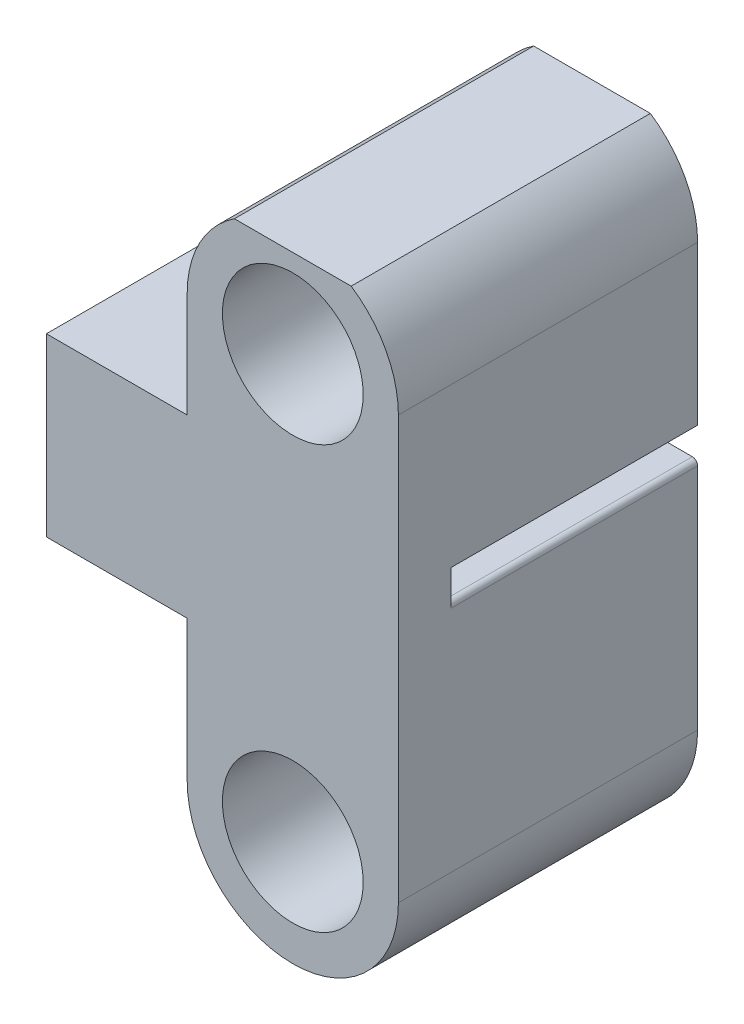
SolidWorks part; units mm, degrees
ref_plane "Front Plane" through (0, 0, 0) normal (0, 0, 1) x (1, 0, 0)
ref_plane "Top Plane" through (0, 0, 0) normal (0, 1, 0) x (1, 0, 0)
ref_plane "Right Plane" through (0, 0, 0) normal (1, 0, 0) x (0, 0, -1)
sketch "Sketch1" plane through (0, 0, 0) normal (0, 0, 1) x (1, 0, 0)
  line L0 (0, 0) -> (0, -12) construction
  line L1 (-3, 0) -> (-3, -12)
  line L2 (3, 0) -> (3, -12)
  arc A0 (3, 0) -> (-3, 0) centre (0, 0) ccw
  arc A1 (-3, -12) -> (3, -12) centre (0, -12) ccw
  circle A2 centre (0, 0) radius 2
  circle A3 centre (0, -12) radius 2
  dimension "D2" = 6
  dimension "D6" = 4
  dimension "D7" = 4
  dimension "D1" = 12
extrude "Boss-Extrude1" add sketch "Sketch1" along normal blind 8.5
sketch "Sketch2" plane through (3, 0, 0) normal (1, 0, 0) x (0, 0, -1)
  line L0 (-8.5, -6) -> (0, -6) construction
  line L1 (-8.5, -12) -> (-8.5, 0) construction
  line L2 (0, -12) -> (0, 0) construction
  line L3 (-4.25, 0) -> (-4.25, -12) construction
  line L4 (-8.5, 0) -> (0, 0) construction
  line L5 (-8.5, -12) -> (0, -12) construction
  circle A0 centre (-4.25, -8.5) radius 2
  dimension "D1" = 4
  dimension "D2" = 2.5
extrude "Cut-Extrude1" [suppressed] cut sketch "Sketch2" against normal through all
sketch "Sketch3" [suppressed] plane through (3, 0, 0) normal (1, 0, 0) x (0, 0, -1)
  line L1 (-0.6416, -8.5) -> (-2.4458, -5.375)
  line L2 (-2.4458, -5.375) -> (-6.0542, -5.375)
  line L3 (-6.0542, -5.375) -> (-7.8584, -8.5)
  line L4 (-7.8584, -8.5) -> (-6.0542, -11.625)
  line L5 (-6.0542, -11.625) -> (-2.4458, -11.625)
  line L6 (-2.4458, -11.625) -> (-0.6416, -8.5)
  line L7 (-1.8684, -4.375) -> (-6.6316, -4.375)
  line L8 (-6.6316, -4.375) -> (-9.0131, -8.5)
  line L9 (-9.0131, -8.5) -> (-6.6316, -12.625)
  line L10 (-6.6316, -12.625) -> (-1.8684, -12.625)
  line L11 (-1.8684, -12.625) -> (0.5131, -8.5)
  line L12 (0.5131, -8.5) -> (-1.8684, -4.375)
  circle A0 centre (-4.25, -8.5) radius 3.125 construction
  circle A1 centre (-4.25, -8.5) radius 4.125 construction
  dimension "D1" = 6.25
  dimension "D2" = 1
extrude "Boss-Extrude2" [suppressed] add sketch "Sketch3" along normal blind 2 and the other way blind 0.5
sketch "Sketch4" [suppressed] plane through (-3, 0, 0) normal (-1, 0, 0) x (0, 0, 1)
  line L0 (4.25, 0) -> (4.25, -6.5) construction
  line L1 (8.5, 0) -> (0, 0) construction
  line L3 (0.75, -2.75) -> (7.75, -2.75)
  line L4 (0.75, -2.75) -> (0.75, -5.75)
  line L5 (0.75, -5.75) -> (7.75, -5.75)
  line L6 (7.75, -2.75) -> (7.75, -5.75)
  line L7 (0.75, -2.75) -> (7.75, -5.75) construction
  line L8 (0.75, -5.75) -> (7.75, -2.75) construction
  circle A0 centre (4.25, -8.5) radius 2 construction
  point P7 (4.25, -4.25)
  dimension "D1" = 7
  dimension "D2" = 3
  dimension "D3" = 2.75
extrude "Cut-Extrude2" [suppressed] cut sketch "Sketch4" against normal through all
sketch "Sketch5" plane through (-3, 0, 0) normal (-1, 0, 0) x (0, 0, 1)
  line L0 (4.25, 0) -> (4.25, -12) construction
  line L1 (8.5, 0) -> (0, 0) construction
  line L2 (8.5, -12) -> (0, -12) construction
  line L3 (0, -6) -> (8.5, -6) construction
  line L4 (0, 0) -> (0, -12) construction
  line L5 (8.5, 0) -> (8.5, -12) construction
  line L7 (0, -15) -> (8.5, -15)
  line L8 (0, -15) -> (0, 3)
  line L9 (0, 3) -> (8.5, 3)
  line L10 (8.5, -15) -> (8.5, 3)
  line L11 (0, -15) -> (8.5, 3) construction
  line L12 (0, 3) -> (8.5, -15) construction
  point P12 (4.25, -6)
extrude "Cut-Extrude3" [suppressed] cut sketch "Sketch5" against normal through all flip side to cut
sketch "Sketch9" plane through (-3, 0, 0) normal (-1, 0, 0) x (0, 0, 1)
  line L0 (8.5, 0) -> (8.5, -12) construction
  line L1 (0, -3) -> (8.5, -3)
  line L2 (0, -3) -> (0, -8)
  line L3 (0, -8) -> (8.5, -8)
  line L4 (8.5, -3) -> (8.5, -8)
  line L5 (0, 0) -> (0, -12) construction
  line L6 (8.5, 0) -> (0, 0) construction
  dimension "D1" = 5
  dimension "D2" = 3
extrude "Boss-Extrude4" add sketch "Sketch9" along normal blind 4
sketch "Sketch6" plane through (3, 0, 0) normal (1, 0, 0) x (0, 0, -1)
  line L0 (0, -12) -> (0, 0) construction
  line L1 (0, -4.5) -> (-7, -4.5)
  line L2 (0, -4.5) -> (0, -6.1)
  line L3 (0, -6.1) -> (-7, -6.1)
  line L4 (-7, -4.5) -> (-7, -6.1)
  dimension "D1" = 1.6
  dimension "D2" = 4.5
  dimension "D3" = 7
extrude "Cut-Extrude5" cut sketch "Sketch6" against normal through all
sketch "Sketch7" plane through (0, 0, 7) normal (0, 0, -1) x (-1, 0, 0)
  line L0 (-3, -6.1) -> (-3, -5.5)
  line L1 (-3, -4.5) -> (-3, -6.1) construction
  line L2 (-2.85, -5.35) -> (-2.15, -5.35)
  line L3 (-2, -5.5) -> (-2, -6.1)
  line L4 (7, -6.1) -> (-3, -6.1) construction
  line L5 (-2, -6.1) -> (-3, -6.1)
  line L6 (-0.85, -5.35) -> (-0.15, -5.35)
  line L7 (0, -5.5) -> (0, -6.1)
  line L8 (0, -6.1) -> (-1, -6.1)
  line L9 (-1, -6.1) -> (-1, -5.5)
  line L10 (1.15, -5.35) -> (1.85, -5.35)
  line L11 (2, -5.5) -> (2, -6.1)
  line L12 (2, -6.1) -> (1, -6.1)
  line L13 (1, -6.1) -> (1, -5.5)
  line L14 (3.15, -5.35) -> (3.85, -5.35)
  line L15 (4, -5.5) -> (4, -6.1)
  line L16 (4, -6.1) -> (3, -6.1)
  line L17 (3, -6.1) -> (3, -5.5)
  line L18 (5.15, -5.35) -> (5.85, -5.35)
  line L19 (6, -5.5) -> (6, -6.1)
  line L20 (6, -6.1) -> (5, -6.1)
  line L21 (5, -6.1) -> (5, -5.5)
  arc A0 (-2.15, -5.35) -> (-2, -5.5) centre (-2.15, -5.5) cw
  arc A1 (-3, -5.5) -> (-2.85, -5.35) centre (-2.85, -5.5) cw
  arc A2 (-1, -5.5) -> (-0.85, -5.35) centre (-0.85, -5.5) cw
  arc A3 (-0.15, -5.35) -> (0, -5.5) centre (-0.15, -5.5) cw
  arc A4 (1, -5.5) -> (1.15, -5.35) centre (1.15, -5.5) cw
  arc A5 (1.85, -5.35) -> (2, -5.5) centre (1.85, -5.5) cw
  arc A6 (3, -5.5) -> (3.15, -5.35) centre (3.15, -5.5) cw
  arc A7 (3.85, -5.35) -> (4, -5.5) centre (3.85, -5.5) cw
  arc A8 (5, -5.5) -> (5.15, -5.35) centre (5.15, -5.5) cw
  arc A9 (5.85, -5.35) -> (6, -5.5) centre (5.85, -5.5) cw
  point P11 (-2, -5.35)
  point P14 (-3, -5.35)
  dimension "D3" = 0.15
  dimension "D1" = 1
  dimension "D2" = 0.75
  dimension "D4" = 5
extrude "Boss-Extrude3" add sketch "Sketch7" along normal through all
sketch "Sketch10" plane through (0, 0, 8.5) normal (0, 0, 1) x (1, 0, 0)
  line L1 (-2.5, 3.5) -> (2.5, 3.5)
  line L2 (-2.5, 3.5) -> (-2.5, 2.5)
  line L3 (-2.5, 2.5) -> (2.5, 2.5)
  line L4 (2.5, 3.5) -> (2.5, 2.5)
  line L5 (-2.5, 3.5) -> (2.5, 2.5) construction
  line L6 (-2.5, 2.5) -> (2.5, 3.5) construction
  arc A0 (3, 0) -> (-3, 0) centre (0, 0) ccw construction
  point P0 (0, 3)
  dimension "D1" = 1
  dimension "D2" = 5
extrude "Cut-Extrude6" cut sketch "Sketch10" against normal through all
equation "\"X-ROD-SPACING\"=45"
equation "\"Y-ROD-SPACING\"=75"
equation "\"Z-ROD-SPACING\"=17.5"
equation "\"Y-BED-OFFSET\"=2"
equation "\"Y-BED-ROD-INSET\"=3.5"
equation "\"Y-BED-SCREW-SPACING\"=209"
equation "\"Y-BED-SCREW-CUTOUT-SLOT-HEIGHT\"=2"
equation "\"T-SLOT-NUT-FILLET-RADIUS\"=0.25"
equation "\"T-SLOT-SCREW-SHAFT-RADIUS\"=1.75"
equation "\"T-SLOT-SCREW-SHAFT-CUTOUT-LENGTH\"=10.5"
equation "\"T-SLOT-NUT-DEPTH\"=4.2"
equation "\"T-SLOT-NUT-WIDTH\"=3"
equation "\"T-SLOT-NUT-END-DISTANCE\"=8"
equation "\"ACRYLIC-THICKNESS\"=10"
equation "\"ACRYLIC-THICKNESS2\"=4.5"
equation "\"ACRYLIC-TAB-CUTOUT-SIZE\"=\"ACRYLIC-THICKNESS\"+\"ACRYLIC-TAB-TOLERANCE\"*2"
equation "\"ACRYLIC-TAB-TOLERANCE\"=.1"
equation "\"ACRYLIC-TAB-WIDTH\"=\"ACRYLIC-THICKNESS\""
equation "\"ACRYLIC-M3-HOLE\"=3.1"
equation "\"SMOOTHROD-CAP-SCREW-DISTANCE\"=20"
equation "\"FRAME-WIDTH-INNER\"=370"
equation "\"NEMA17-HOLE-SPACING\"=31"
equation "\"NEMA17-CENTRAL-CUTOUT\"=22.5"
equation "\"Z-BRACKET-REACH\"=55"
equation "\"Z-ROD-INSET\"=16"
equation "\"TOP-BRACKET-SPACING\"=40"
equation "\"SMOOTHROD-X-LENGTH\"=350"
equation "\"SMOOTHROD-Y-LENGTH\"=350"
equation "\"SMOOTHROD-Z-LENGTH\"=350"
equation "\"SMOOTHROD-TIGHTENING-HEADROOM\"=.25"
equation "\"LEADSCREW-Z-LENGTH\"=300"
equation "\"SCREW-LENGTH-FRAME\"=\"ACRYLIC-THICKNESS\" + 10"
equation "\"SCREW-LENGTH-MOTOR\"=\"ACRYLIC-THICKNESS\" + 5"
equation "\"SCREW-LENGTH-EXTRUDER\"=28"
equation "\"SCREW-HEAD-RADIUS\"=6"
equation "\"PRINTED-M3-HOLE\"=3.5"
equation "\"PRINTED-X-SMOOTHROD-DIAMETER\"=8.2"
equation "\"PRINTED-X-SMOOTHROD-CUTOUT\"=10"
equation "\"PRINTED-X-BASE-HEIGHT\"=10"
equation "\"PRINTED-LM8UU-CUTOUT-SIZE\"=15.25"
equation "\"PRINTED-LM8UU-CUTOUT-LENGTH\"=24.5"
equation "\"PRINTED-X-IDLER-HEIGHT\"=16"
equation "\"PRINTED-M3-NUT-AF\"=6.25"
equation "\"PSU-MOUNTING-WIDTH\"=95"
equation "\"PSU-MOUNTING-HEIGHT\"=177"
equation "\"Y-BELT-TO-ROD-DISTANCE\"=20"
equation "\"SPOOL-HOLDER-ROD-SPACING\"=150"
equation "\"ACRYLIC-X-CARRIAGE-WIDTH\"=55"
equation "\"ACRYLIC-X-CARRIAGE-HEIGHT\"=75"
equation "\"ACRYLIC-X-CARRIAGE-LM8UU-CUTOUT-WIDTH\"=24.25"
equation "\"ACRYLIC-X-CARRIAGE-LM8UU-CUTOUT-HEIGHT\"=11.5"
equation "\"ACRYLIC-X-CARRIAGE-SCREW-SPACING-X\"=15"
equation "\"ACRYLIC-X-CARRIAGE-SCREW-SPACING-Y\"=33"
equation "\"ACRYLIC-X-CARRIAGE-CENTER-TAB-SPACING\"=14"
equation "\"ACRYLIC-X-CARRIAGE-EXTRUDER-OFFSET\"=26"
equation "\"ACRYLIC-X-CARRIAGE-EXTRUDER-ANGLE\"=90"
equation "\"ACRYLIC-X-CARRIAGE-EXTRUDER-SHELF-DEPTH\"=\"ACRYLIC-X-CARRIAGE-EXTRUDER-OFFSET\" + 28"
equation "\"ACRYLIC-X-CARRIAGE-EXTRUDER-BRACE-SPACING\"=23"
equation "\"ACRYLIC-X-CARRIAGE-EXTRUDER-BRACE-TAB-OFFSET\"=20"
equation "\"ACRYLIC-X-CARRIAGE-EXTRUDER-BRACE-HEIGHT\"=35"
equation "\"ACRYLIC-X-CARRIAGE-EXTRUDER-BRACE-SCREW-SPACING\"=22"
equation "\"ACRYLIC-X-CARRIAGE-DUAL-WIDTH-MULTIPLIER\"=1.65"
equation "\"ACRYLIC-X-CARRIAGE-DUAL-HOTEND-SPACING\"=42"
equation "\"ACRYLIC-X-CARRIAGE-DUAL-WIDTH\"=95"
equation "\"ACRYLIC-X-CARRIAGE-DUAL-HOTEND-SEPARATION\"=35"
equation "\"ACRYLIC-X-CARRIAGE-DUAL-MOUNT-PLATE-DEPTH\"=75"
equation "\"ACRYLIC-X-CARRIAGE-DUAL-MOUNT-BRACE-WIDTH\"=33"
equation "\"ACRYLIC-X-CARRIAGE-DUAL-MOUNT-SCREW-WIDTH\"=40"
equation "\"BLOWER-FAN-WIDTH\"=15"
equation "\"D1@Sketch3\"=\"PRINTED-M3-NUT-AF\""
